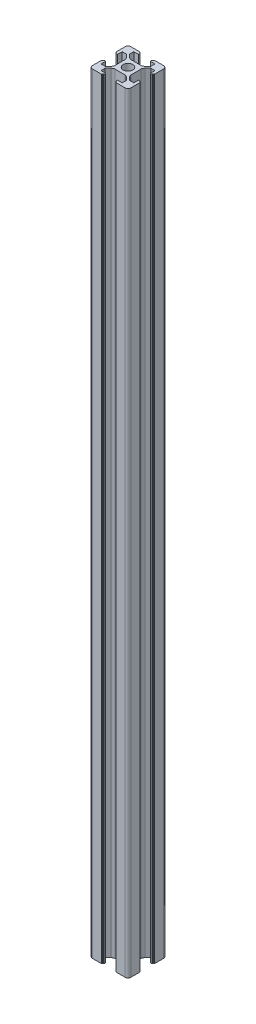
SolidWorks part; units mm, degrees
ref_plane "Front Plane" through (0, 0, 0) normal (0, 0, 1) x (1, 0, 0)
ref_plane "Top Plane" through (0, 0, 0) normal (0, 1, 0) x (1, 0, 0)
ref_plane "Right Plane" through (0, 0, 0) normal (1, 0, 0) x (0, 0, -1)
sketch "Sketch1" plane through (0, 0, 0) normal (0, 1, 0) x (1, 0, 0)
  line L0 (-8.5, 8.5) -> (8.5, 8.5)
  line L1 (-8.5, -10) -> (8.5, -10)
  line L2 (-10, -8.5) -> (-10, 8.5)
  line L3 (-8.5, 10) -> (8.5, 10)
  line L4 (10, -8.5) -> (10, 8.5)
  line L5 (-10, -10) -> (10, 10) construction
  line L6 (-10, 10) -> (10, -10) construction
  line L7 (8.5, -8.5) -> (8.5, 8.5)
  line L8 (-8.5, -8.5) -> (8.5, -8.5)
  line L9 (-8.5, -8.5) -> (-8.5, 8.5)
  line L10 (-10.4243, 9.5757) -> (9.5757, -10.4243)
  line L11 (-9.5757, -10.4243) -> (10.4243, 9.5757)
  line L12 (-9.5757, 10.4243) -> (10.4243, -9.5757)
  line L13 (-10.4243, -9.5757) -> (9.5757, 10.4243)
  line L14 (-9.5, -8.5) -> (-9.5, 8.5)
  line L15 (-10, -5.5) -> (10, -5.5)
  line L16 (-10, -5.5) -> (-10, 5.5)
  line L17 (-10, 5.5) -> (10, 5.5)
  line L18 (10, -5.5) -> (10, 5.5)
  line L19 (-10, -5.5) -> (10, 5.5) construction
  line L20 (-10, 5.5) -> (10, -5.5) construction
  line L21 (5.5, -10) -> (-5.5, -10)
  line L22 (5.5, -10) -> (5.5, 10)
  line L23 (5.5, 10) -> (-5.5, 10)
  line L24 (-5.5, -10) -> (-5.5, 10)
  line L25 (5.5, -10) -> (-5.5, 10) construction
  line L26 (5.5, 10) -> (-5.5, -10) construction
  line L27 (10, -3.1) -> (-10, -3.1)
  line L28 (10, -3.1) -> (10, 3.1)
  line L29 (10, 3.1) -> (-10, 3.1)
  line L30 (-10, -3.1) -> (-10, 3.1)
  line L31 (10, -3.1) -> (-10, 3.1) construction
  line L32 (10, 3.1) -> (-10, -3.1) construction
  line L33 (10, -3.6) -> (-10, -3.6)
  line L34 (10, -3.6) -> (10, 3.6)
  line L35 (10, 3.6) -> (-10, 3.6)
  line L36 (-10, -3.6) -> (-10, 3.6)
  line L37 (10, -3.6) -> (-10, 3.6) construction
  line L38 (10, 3.6) -> (-10, -3.6) construction
  line L39 (-8.5, 9.5) -> (8.5, 9.5)
  line L40 (9.5, -8.5) -> (9.5, 8.5)
  line L41 (-8.5, -9.5) -> (8.5, -9.5)
  arc A0 (-8.5, 10) -> (-10, 8.5) centre (-8.5, 8.5) ccw
  arc A1 (10, 8.5) -> (8.5, 10) centre (8.5, 8.5) ccw
  arc A2 (8.5, -10) -> (10, -8.5) centre (8.5, -8.5) ccw
  arc A3 (-10, -8.5) -> (-8.5, -10) centre (-8.5, -8.5) ccw
  arc A4 (8.5, 8.5) -> (8.5, 8.5) centre (8.5, 8.5) ccw
  arc A5 (8.5, -8.5) -> (8.5, -8.5) centre (8.5, -8.5) ccw
  arc A6 (-8.5, -8.5) -> (-8.5, -8.5) centre (-8.5, -8.5) ccw
  arc A7 (-8.5, 8.5) -> (-8.5, 8.5) centre (-8.5, 8.5) ccw
  circle A8 centre (0, 0) radius 2.5
  arc A9 (-8.5, 9.5) -> (-9.5, 8.5) centre (-8.5, 8.5) ccw
  arc A10 (9.5, 8.5) -> (8.5, 9.5) centre (8.5, 8.5) ccw
  arc A11 (8.5, -9.5) -> (9.5, -8.5) centre (8.5, -8.5) ccw
  arc A12 (-9.5, -8.5) -> (-8.5, -9.5) centre (-8.5, -8.5) ccw
  point P0 (0, 0)
  point P38 (0, 0)
  point P43 (0, 0)
  dimension "D3" = 1.5
  dimension "D4" = 1.5
  dimension "D5" = 1.5
  dimension "D6" = 1.5
  dimension "D12" = 5
  dimension "D1" = 20
  dimension "D2" = 20
  dimension "D10" = 11
  dimension "D11" = 11
  dimension "D13" = 6.2
  dimension "D14" = 7.2
  dimension "D7" = 1.5
  dimension "D8" = 0.6
  dimension "D9" = 0.6
  dimension "D15" = 0.5
sketch "Sketch2" plane through (0, 0, 0) normal (0, 1, 0) x (1, 0, 0)
  line L0 (-10, -8.5) -> (-10, 8.5) construction
  line L1 (-8.5, 10) -> (8.5, 10) construction
  line L2 (10, -8.5) -> (10, 8.5) construction
  line L3 (-8.5, -10) -> (8.5, -10) construction
  line L4 (-10, -8.5) -> (-10, 8.5)
  line L5 (-8.5, 10) -> (8.5, 10)
  line L6 (10, -8.5) -> (10, 8.5)
  line L7 (-8.5, -10) -> (8.5, -10)
  arc A0 (-8.5, 10) -> (-10, 8.5) centre (-8.5, 8.5) ccw construction
  arc A1 (10, 8.5) -> (8.5, 10) centre (8.5, 8.5) ccw construction
  arc A2 (8.5, -10) -> (10, -8.5) centre (8.5, -8.5) ccw construction
  arc A3 (-10, -8.5) -> (-8.5, -10) centre (-8.5, -8.5) ccw construction
  arc A4 (-8.5, 10) -> (-10, 8.5) centre (-8.5, 8.5) ccw
  arc A5 (10, 8.5) -> (8.5, 10) centre (8.5, 8.5) ccw
  arc A6 (8.5, -10) -> (10, -8.5) centre (8.5, -8.5) ccw
  arc A7 (-10, -8.5) -> (-8.5, -10) centre (-8.5, -8.5) ccw
extrude "Boss-Extrude1" add sketch "Sketch2" along normal blind 400
sketch "Sketch3" plane through (0, 400, 0) normal (0, 1, 0) x (1, 0, 0)
  line L3 (4.2, -4.2) -> (-4.2, -4.2)
  line L4 (4.2, -4.2) -> (4.2, 4.2)
  line L5 (4.2, 4.2) -> (-4.2, 4.2)
  line L6 (-4.2, -2.523) -> (-4.2, 2.523)
  line L7 (4.2, -4.2) -> (-4.2, 4.2) construction
  line L8 (4.2, 4.2) -> (-4.2, -4.2) construction
  line L10 (-10.4243, 9.5757) -> (9.5757, -10.4243) construction
  line L11 (-9.5757, 10.4243) -> (10.4243, -9.5757) construction
  line L12 (-10.4243, 9.5757) -> (-4.7858, 3.9373)
  line L13 (-9.5757, 10.4243) -> (10.4243, -9.5757)
  line L15 (-8.5, -8.5) -> (-8.5, 8.5) construction
  line L16 (-8.5, -8.5) -> (-8.5, -3.1)
  line L17 (-10, 5.5) -> (10, 5.5) construction
  line L19 (10, -3.1) -> (-10, -3.1) construction
  line L20 (10, -3.6) -> (-10, -3.6) construction
  line L22 (10, 3.6) -> (-10, 3.6) construction
  line L23 (-10, -8.5) -> (-10, 8.5) construction
  line L24 (-10.4243, -9.5757) -> (9.5757, 10.4243) construction
  line L25 (-8.5, 5.5) -> (10, 5.5)
  line L26 (-10, -5.5) -> (10, -5.5) construction
  line L27 (10, -3.1) -> (-4.2, -3.1)
  line L28 (10, -3.6) -> (-4.4485, -3.6)
  line L29 (-10, -5.5) -> (10, -5.5)
  line L30 (10, 3.6) -> (-4.4485, 3.6)
  line L31 (-10, -8.5) -> (-10, -3.8)
  line L32 (-10.4243, -9.5757) -> (-4.7858, -3.9373)
  line L33 (-10, 3.8) -> (-10, 8.5)
  line L34 (10, 3.1) -> (-10, 3.1) construction
  line L35 (10, 3.1) -> (-4.2, 3.1)
  line L36 (-9.5, -3.6) -> (-9.8, -3.6)
  line L37 (-8.5, -3.1) -> (-9.3, -3.1)
  line L38 (-9.5, 3.3) -> (-9.5, 3.6)
  line L39 (-8.5, 3.1) -> (-8.5, 8.5)
  line L40 (-9.5, 3.6) -> (-9.8, 3.6)
  line L41 (-9.5, -3.6) -> (-9.5, -3.3)
  line L42 (4.6515, -5.5) -> (10, -5.5)
  line L43 (-8.5, 3.1) -> (-9.3, 3.1)
  line L44 (-9.5, -8.5) -> (-9.5, 8.5) construction
  line L45 (-10, -8.5) -> (-10, 8.5)
  arc A0 (-9.8, -3.6) -> (-10, -3.8) centre (-9.8, -3.8) ccw
  arc A1 (-9.3, -3.1) -> (-9.5, -3.3) centre (-9.3, -3.3) ccw
  arc A2 (-9.5, 3.3) -> (-9.3, 3.1) centre (-9.3, 3.3) ccw
  arc A3 (-10, 3.8) -> (-9.8, 3.6) centre (-9.8, 3.8) ccw
  arc A4 (-4.7858, 3.9373) -> (-4.2, 2.523) centre (-6.2, 2.523) cw
  arc A5 (-4.2, -2.523) -> (-4.7858, -3.9373) centre (-6.2, -2.523) cw
  circle A6 centre (0, 0) radius 2.5 construction
  circle A7 centre (0, 0) radius 2.5
  point P0 (0, 0)
  point P12 (-4.1093, 4.1093)
  point P40 (-9.5, -3.6)
  point P46 (-9.5, 3.6)
  point P47 (-5.2042, 5.2042)
  point P55 (-9.5, 3.1)
  line M12 (-10, 8.5) -> (-10, -8.5)
  dimension "D2" = 0.2
  dimension "D3" = 0.2
  dimension "D4" = 0.2
  dimension "D5" = 0.2
  dimension "D1" = 2
  dimension "D6" = 2
  dimension "D7" = 4.3
extrude "Cut-Extrude1" cut sketch "Sketch3" against normal through all contours L39 L43 L38 L40 L36 L41 L37 L16 L29 L32 L6 L12 L25 M12 | L13 A7 | L13 A7 region at (-0.5269, 400, 0.5269) region at (0.9842, 400, -0.9842) region at (-7.033, 400, 0)
ref_axis "Axis1" through (0, -20, 0) along (0, 1, 0)
pattern_circular "CirPattern1" count 4 over 360 about axis through (0, -20, 0) along (0, 1, 0) of "Cut-Extrude1"
